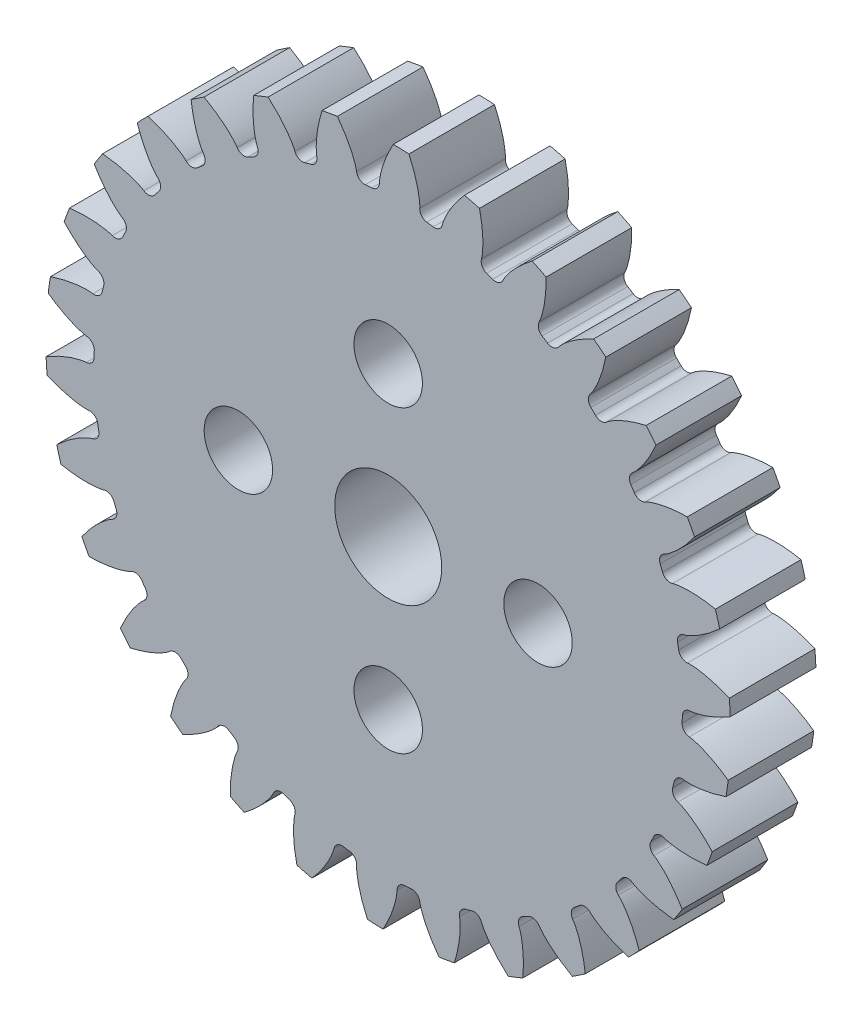
SolidWorks part; units mm, degrees
material "AISI 304"
ref_plane "前基準面" through (0, 0, 0) normal (0, 0, 1) x (1, 0, 0)
ref_plane "上基準面" through (0, 0, 0) normal (0, 1, 0) x (1, 0, 0)
ref_plane "右基準面" through (0, 0, 0) normal (1, 0, 0) x (0, 0, -1)
sketch "草圖1" plane through (0, 0, 0) normal (0, 0, 1) x (1, 0, 0)
  spline S0 degree 4 poles (14.0954, 0) (14.1018, 0.0001) (14.1198, 0.0007) (14.1539, 0.0032) (14.2093, 0.0092) (14.2797, 0.0194) (14.3703, 0.0358) (14.4765, 0.0591) (14.5926, 0.0888) (14.7181, 0.1257) (14.8425, 0.1663) (14.9657, 0.2105) (15.0877, 0.2578) (15.2344, 0.3189) (15.4088, 0.3975) (15.6103, 0.497) (15.8359, 0.6188) (16.0623, 0.7523) (16.282, 0.8915) (16.5004, 1.0407) (16.709, 1.1913) (16.9216, 1.3564) (17.1157, 1.5133) (17.3284, 1.6984) (17.4985, 1.8506) (17.7175, 2.0611) (17.8452, 2.1884) (17.9927, 2.3407) (18.0571, 2.41) (18.0968, 2.4527) knots 0 0 0 0 0 0.005377 0.015084 0.028532 0.04661 0.064855 0.092111 0.119476 0.146842 0.174209 0.201575 0.228941 0.256307 0.307035 0.361767 0.4165 0.471232 0.525964 0.580697 0.635429 0.690161 0.744894 0.799626 0.854358 0.909091 0.954545 1 1 1 1 1 construction
  spline S1 degree 4 poles (14.0954, 0) (14.1018, 0.0001) (14.1198, 0.0007) (14.1539, 0.0032) (14.2093, 0.0092) (14.2797, 0.0194) (14.3703, 0.0358) (14.4765, 0.0591) (14.5926, 0.0888) (14.7181, 0.1257) (14.8425, 0.1663) (14.9657, 0.2105) (15.0877, 0.2578) (15.2344, 0.3189) (15.4088, 0.3975) (15.6103, 0.497) (15.8359, 0.6188) (16.0623, 0.7523) (16.282, 0.8915) (16.5004, 1.0407) (16.709, 1.1913) (16.9216, 1.3564) (17.1157, 1.5133) (17.3284, 1.6984) (17.4985, 1.8506) (17.6701, 2.0155) (17.7529, 2.0969) (17.795, 2.1389) knots 0 0 0 0 0 0.005377 0.015084 0.028532 0.04661 0.064855 0.092111 0.119476 0.146842 0.174209 0.201575 0.228941 0.256307 0.307035 0.361767 0.4165 0.471232 0.525964 0.580697 0.635429 0.690161 0.744894 0.799626 0.854358 0.909091 0.909091 0.909091 0.909091 0.909091
sketch "草圖2" plane through (0, 0, 0) normal (0, 0, 1) x (1, 0, 0)
  line L0 (0, 0) -> (18.382, 0) construction
  line L1 (0, 0) -> (14.9893, -0.5663) construction
  line L2 (14.0954, 0) -> (13.75, 0)
  line L3 (14.0552, -1.0635) -> (13.7108, -1.0375)
  circle A0 centre (0, 0) radius 13.75
  circle A1 centre (0, 0) radius 14.095
  circle A2 centre (0, 0) radius 16
  arc A3 (14.9893, -0.5663) -> (14.9983, 0.2236) centre (0, 0) ccw
  spline S0 degree 4 poles (-11.7122, 1999.7464) (11.9224, 24.6588) (12.6817, 0.3712) (13.4603, -0.0709) (14.2093, 0.0092) (14.2797, 0.0194) (14.3703, 0.0358) (14.4765, 0.0591) (14.5926, 0.0888) (14.7181, 0.1257) (14.8425, 0.1663) (14.9657, 0.2105) (15.0877, 0.2578) (15.2344, 0.3189) (15.4088, 0.3975) (15.6103, 0.497) (15.8359, 0.6188) (16.0623, 0.7523) (16.282, 0.8915) (16.5004, 1.0407) (16.709, 1.1913) (16.9216, 1.3564) (17.1157, 1.5133) (17.3284, 1.6984) (18.2216, 2.4971) (21.0215, 5.5124) (-18.2543, -33.3642) (1431.3698, 1416.8324) knots -0.583363 -0.583363 -0.583363 -0.583363 -0.583363 0.005377 0.015084 0.028532 0.04661 0.064855 0.092111 0.119476 0.146842 0.174209 0.201575 0.228941 0.256307 0.307035 0.361767 0.4165 0.471232 0.525964 0.580697 0.635429 0.690161 0.744894 0.799626 0.854358 1.839209 1.839209 1.839209 1.839209 1.839209 only from (14.0954, 0) to (17.795, 2.1389) construction
  spline S1 degree 4 poles (14.0954, 0) (14.1018, 0.0001) (14.1198, 0.0007) (14.1539, 0.0032) (14.2093, 0.0092) (14.2797, 0.0194) (14.3703, 0.0358) (14.4765, 0.0591) (14.5926, 0.0888) (14.7181, 0.1257) (14.8425, 0.1663) (14.9657, 0.2105) (15.0877, 0.2578) (15.2344, 0.3189) (15.4088, 0.3975) (15.6103, 0.497) (15.8359, 0.6188) (16.0623, 0.7523) (16.282, 0.8915) (16.5004, 1.0407) (16.709, 1.1913) (16.9216, 1.3564) (17.1157, 1.5133) (17.3284, 1.6984) (17.4985, 1.8506) (17.6701, 2.0155) (17.7529, 2.0969) (17.795, 2.1389) knots 0 0 0 0 0 0.005377 0.015084 0.028532 0.04661 0.064855 0.092111 0.119476 0.146842 0.174209 0.201575 0.228941 0.256307 0.307035 0.361767 0.4165 0.471232 0.525964 0.580697 0.635429 0.690161 0.744894 0.799626 0.854358 0.909091 0.909091 0.909091 0.909091 0.909091
  spline S2 degree 4 poles (14.0552, -1.0635) (14.0616, -1.0641) (14.0795, -1.0661) (14.1133, -1.0712) (14.1681, -1.0813) (14.2375, -1.0968) (14.3266, -1.12) (14.4308, -1.1512) (14.5443, -1.1896) (14.6667, -1.2358) (14.7876, -1.2858) (14.9072, -1.3391) (15.0252, -1.3955) (15.1669, -1.4675) (15.3349, -1.559) (15.5283, -1.6734) (15.7441, -1.8119) (15.9597, -1.9621) (16.1684, -2.1175) (16.3748, -2.2828) (16.5715, -2.4487) (16.771, -2.6293) (16.9528, -2.8004) (17.1508, -3.001) (17.309, -3.1656) (17.4676, -3.343) (17.5441, -3.4304) (17.5829, -3.4755) knots 0 0 0 0 0 0.005377 0.015084 0.028532 0.04661 0.064855 0.092111 0.119476 0.146842 0.174209 0.201575 0.228941 0.256307 0.307035 0.361767 0.4165 0.471232 0.525964 0.580697 0.635429 0.690161 0.744894 0.799626 0.854358 0.909091 0.909091 0.909091 0.909091 0.909091
  dimension "D1" = 30
  dimension "D2" = 32
  dimension "D3" = 27.5
  dimension "D4" = 28.19
  dimension "D5" = 0.79
extrude "填料-伸長1" add sketch "草圖2" along normal blind 4 contours A2
sketch "草圖3" plane through (0, 0, 4) normal (0, 0, 1) x (1, 0, 0)
  line L0 (14.0552, -1.0635) -> (13.7108, -1.0375) construction
  line L1 (14.0954, 0) -> (13.75, 0) construction
  line L2 (14.0552, -1.0635) -> (13.7108, -1.0375)
  line L3 (14.0954, 0) -> (13.75, 0)
  circle A0 centre (0, 0) radius 16 construction
  circle A1 centre (0, 0) radius 13.75 construction
  arc A2 (15.8854, -1.9114) -> (15.9844, 0.7073) centre (0, 0) ccw
  arc A3 (13.7108, -1.0375) -> (13.75, 0) centre (0, 0) ccw
  spline S0 degree 4 poles (-162.5651, -1993.1622) (10.0278, -25.4881) (12.6175, -1.3271) (13.4273, -0.9449) (14.1681, -1.0813) (14.2375, -1.0968) (14.3266, -1.12) (14.4308, -1.1512) (14.5443, -1.1896) (14.6667, -1.2358) (14.7876, -1.2858) (14.9072, -1.3391) (15.0252, -1.3955) (15.1669, -1.4675) (15.3349, -1.559) (15.5283, -1.6734) (15.7441, -1.8119) (15.9597, -1.9621) (16.1684, -2.1175) (16.3748, -2.2828) (16.5715, -2.4487) (16.771, -2.6293) (16.9528, -2.8004) (17.1508, -3.001) (17.9812, -3.8649) (20.5456, -7.0828) (-15.6849, 34.6464) (1320.3857, -1520.7943) knots -0.583363 -0.583363 -0.583363 -0.583363 -0.583363 0.005377 0.015084 0.028532 0.04661 0.064855 0.092111 0.119476 0.146842 0.174209 0.201575 0.228941 0.256307 0.307035 0.361767 0.4165 0.471232 0.525964 0.580697 0.635429 0.690161 0.744894 0.799626 0.854358 1.839209 1.839209 1.839209 1.839209 1.839209 only from (14.0552, -1.0635) to (17.5829, -3.4755) construction
  spline S1 degree 4 poles (-11.7122, 1999.7464) (11.9224, 24.6588) (12.6817, 0.3712) (13.4603, -0.0709) (14.2093, 0.0092) (14.2797, 0.0194) (14.3703, 0.0358) (14.4765, 0.0591) (14.5926, 0.0888) (14.7181, 0.1257) (14.8425, 0.1663) (14.9657, 0.2105) (15.0877, 0.2578) (15.2344, 0.3189) (15.4088, 0.3975) (15.6103, 0.497) (15.8359, 0.6188) (16.0623, 0.7523) (16.282, 0.8915) (16.5004, 1.0407) (16.709, 1.1913) (16.9216, 1.3564) (17.1157, 1.5133) (17.3284, 1.6984) (18.2216, 2.4971) (21.0215, 5.5124) (-18.2543, -33.3642) (1431.3698, 1416.8324) knots -0.583363 -0.583363 -0.583363 -0.583363 -0.583363 0.005377 0.015084 0.028532 0.04661 0.064855 0.092111 0.119476 0.146842 0.174209 0.201575 0.228941 0.256307 0.307035 0.361767 0.4165 0.471232 0.525964 0.580697 0.635429 0.690161 0.744894 0.799626 0.854358 1.839209 1.839209 1.839209 1.839209 1.839209 only from (14.0954, 0) to (17.795, 2.1389) construction
  spline S2 degree 4 poles (14.0552, -1.0635) (14.0616, -1.0641) (14.0795, -1.0661) (14.1133, -1.0712) (14.1681, -1.0813) (14.2375, -1.0968) (14.3266, -1.12) (14.4308, -1.1512) (14.5443, -1.1896) (14.6667, -1.2358) (14.7876, -1.2858) (14.9072, -1.3391) (15.0252, -1.3955) (15.1669, -1.4675) (15.3349, -1.559) (15.5283, -1.6734) (15.6978, -1.7822) (15.8148, -1.8619) (15.8769, -1.9054) (15.8854, -1.9114) knots 0 0 0 0 0 0.005377 0.015084 0.028532 0.04661 0.064855 0.092111 0.119476 0.146842 0.174209 0.201575 0.228941 0.256307 0.307035 0.361767 0.4165 0.425166 0.425166 0.425166 0.425166 0.425166
  spline S3 degree 4 poles (14.0954, 0) (14.1018, 0.0001) (14.1198, 0.0007) (14.1539, 0.0032) (14.2093, 0.0092) (14.2797, 0.0194) (14.3703, 0.0358) (14.4765, 0.0591) (14.5926, 0.0888) (14.7181, 0.1257) (14.8425, 0.1663) (14.9657, 0.2105) (15.0877, 0.2578) (15.2344, 0.3189) (15.4088, 0.3975) (15.6103, 0.497) (15.7875, 0.5927) (15.9102, 0.6633) (15.9754, 0.702) (15.9844, 0.7073) knots 0 0 0 0 0 0.005377 0.015084 0.028532 0.04661 0.064855 0.092111 0.119476 0.146842 0.174209 0.201575 0.228941 0.256307 0.307035 0.361767 0.4165 0.425166 0.425166 0.425166 0.425166 0.425166
extrude "除料-伸長1" cut sketch "草圖3" against normal blind 4
fillet "圓角1" radius 0.38 2 edges at (13.7108, -1.0375, 2) (13.75, 0, 2)
pattern_circular "環狀複製排列1" count 30 over 360 about axis through (0, 0, 4) along (0, 0, -1) of "圓角1", "除料-伸長1"
sketch "草圖4" plane through (0, 0, 4) normal (0, 0, 1) x (1, 0, 0)
  line L0 (0, 0) -> (7, 0) construction
  circle A0 centre (7, 0) radius 1.6
  dimension "D1" = 3.2
  dimension "D2" = 7
extrude "除料-伸長2" cut sketch "草圖4" against normal blind 4
pattern_circular "環狀複製排列2" count 4 over 360 about axis through (0, 0, 0) along (0, 0, 1) of "除料-伸長2" reverse direction yes
sketch "草圖6" plane through (0, 0, 4) normal (0, 0, 1) x (1, 0, 0)
  circle A0 centre (0, 0) radius 2.5
  dimension "D1" = 5
extrude "除料-伸長3" cut sketch "草圖6" against normal blind 10
sketch "草圖5" plane through (0, 0, 4) normal (0, 0, 1) x (1, 0, 0)
  circle A0 centre (0, 0) radius 15 construction
  dimension "D1" = 30
equation "\"a\"= 20"
equation "\"M\"= 1"
equation "\"T\"= 30"
equation "\"R\"= 0.38 * \"M\""
equation "\"D\"= \"M\" * \"T\""
equation "\"Da\"= ( \"T\" + 2 ) * \"M\""
equation "\"Df\"= ( \"T\" - 2.5 ) * \"M\""
equation "\"Db\"= \"M\" * \"T\" * cos ( \"a\" )"
equation "\"rb\"= \"Db\" / 2"
equation "\"S\"= pi * \"M\" * 0.5"
